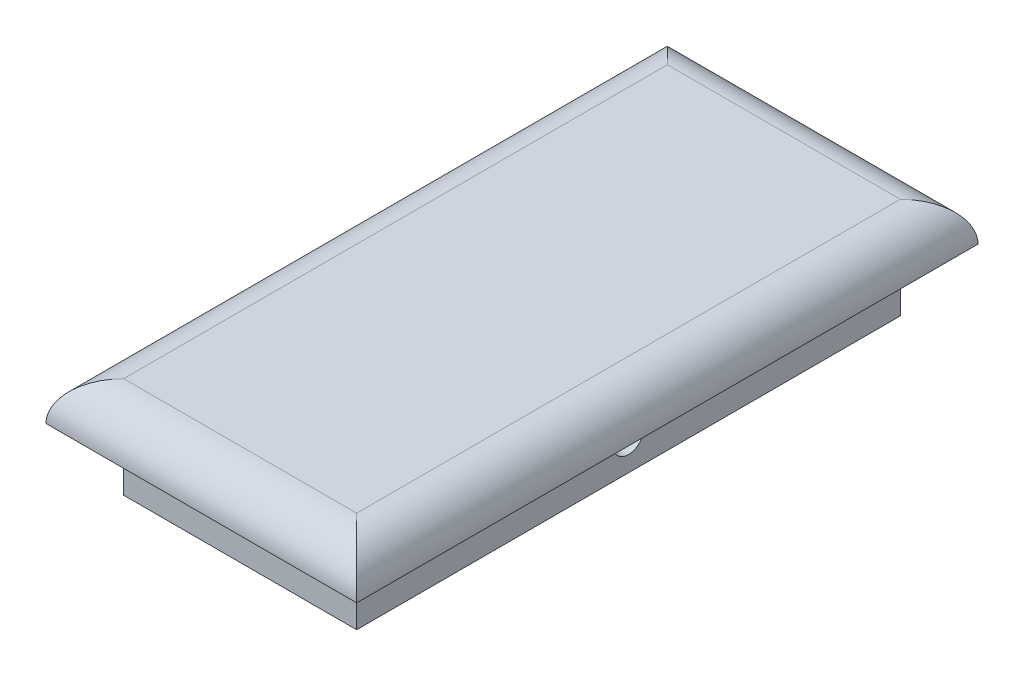
SolidWorks part; units mm, degrees
ref_plane "Front Plane" through (0, 0, 0) normal (0, 0, 1) x (1, 0, 0)
ref_plane "Top Plane" through (0, 0, 0) normal (0, 1, 0) x (1, 0, 0)
ref_plane "Right Plane" through (0, 0, 0) normal (1, 0, 0) x (0, 0, -1)
sketch "Sketch1" plane through (0, 0, 0) normal (0, 1, 0) x (1, 0, 0)
  line L1 (-9.525, -22.225) -> (9.525, -22.225)
  line L2 (-9.525, -22.225) -> (-9.525, 22.225)
  line L3 (-9.525, 22.225) -> (9.525, 22.225)
  line L4 (9.525, -22.225) -> (9.525, 22.225)
  line L5 (-9.525, -22.225) -> (9.525, 22.225) construction
  line L6 (-9.525, 22.225) -> (9.525, -22.225) construction
  point P0 (0, 0)
  dimension "D1" = 19.05
  dimension "D2" = 44.45
extrude "Boss-Extrude1" add sketch "Sketch1" along normal blind 5.08
sketch "Sketch2" plane through (0, 5.08, 0) normal (0, 1, 0) x (1, 0, 0)
  line L0 (-9.525, 22.225) -> (-9.525, -22.225) construction
  line L1 (-12.7, -25.4) -> (12.7, -25.4)
  line L2 (-12.7, -25.4) -> (-12.7, 25.4)
  line L3 (-12.7, 25.4) -> (12.7, 25.4)
  line L4 (12.7, -25.4) -> (12.7, 25.4)
  line L5 (-12.7, -25.4) -> (12.7, 25.4) construction
  line L6 (-12.7, 25.4) -> (12.7, -25.4) construction
  line L7 (9.525, 22.225) -> (-9.525, 22.225) construction
  point P0 (0, 0)
  dimension "D1" = 3.175
  dimension "D2" = 3.175
extrude "Boss-Extrude2" add sketch "Sketch2" along normal blind 3.175
fillet "Fillet1" radius 3.175 4 edges at (0, 8.255, -25.4) (-12.7, 8.255, 0) (0, 8.255, 25.4) (12.7, 8.255, 0)
sketch "Sketch3" plane through (9.525, 0, 0) normal (1, 0, 0) x (0, 0, -1)
  line L0 (-22.225, 2.54) -> (22.225, 2.54) construction
  line L1 (-22.225, 5.08) -> (-22.225, 0) construction
  line L2 (22.225, 5.08) -> (22.225, 0) construction
  point P6 (0, 2.54)
hole_wizard "Tap Drill for M3x0.5 Tap1" positions "3DSketch1" profile "Sketch4" hole size "M3x0.5" standard "ANSI Metric" end condition through all
sketch3d "3DSketch1"
  point P0 (9.525, 2.54, 0)
sketch "Sketch4" plane through (9.525, 2.54, 0) normal (0, 1, 0) x (0, 0, -1)
  line L0 (0, 0) -> (0, 22.225)
  line L1 (0, 22.225) -> (1.25, 22.225)
  line L2 (1.25, 22.225) -> (1.25, 0)
  line L5 (1.25, 0) -> (0, 0)
  line L11 (0, -6.35) -> (0, 107.95) construction
  dimension "Thru Hole Dia." = 2.5
  dimension "Thru Hole Depth" = 22.225
equation "\"D2@Sketch2\"=\"D1@Sketch2\""
